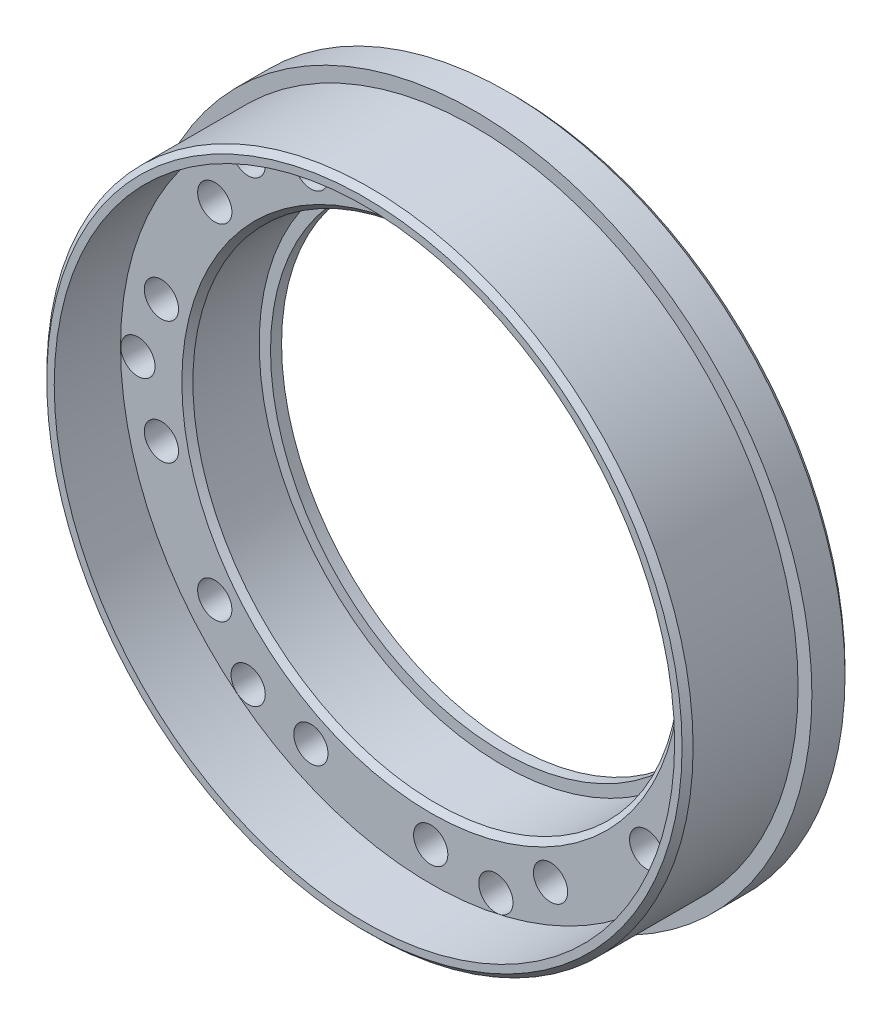
SolidWorks part; units mm, degrees
ref_plane "Front Plane" through (0, 0, 0) normal (0, 0, 1) x (1, 0, 0)
ref_plane "Top Plane" through (0, 0, 0) normal (0, 1, 0) x (1, 0, 0)
ref_plane "Right Plane" through (0, 0, 0) normal (1, 0, 0) x (0, 0, -1)
sketch "Sketch1" plane through (0, 0, 0) normal (0, 0, 1) x (1, 0, 0)
  line L0 (0, 0) -> (0, 34.3477) construction
  circle A0 centre (0, 0) radius 29.25
  circle A1 centre (0, 0) radius 30.5
  circle A2 centre (0, 0) radius 22.025
  circle A3 centre (0, 25) radius 1.55
  circle A4 centre (10.8471, 22.5242) radius 1.55
  circle A5 centre (19.5458, 15.5872) radius 1.55
  circle A6 centre (24.3732, 5.563) radius 1.55
  circle A7 centre (24.3732, -5.563) radius 1.55
  circle A8 centre (19.5458, -15.5872) radius 1.55
  circle A9 centre (10.8471, -22.5242) radius 1.55
  circle A10 centre (0, -25) radius 1.55
  circle A11 centre (-10.8471, -22.5242) radius 1.55
  circle A12 centre (-19.5458, -15.5872) radius 1.55
  circle A13 centre (-24.3732, -5.563) radius 1.55
  circle A14 centre (-24.3732, 5.563) radius 1.55
  circle A15 centre (-19.5458, 15.5872) radius 1.55
  circle A16 centre (-10.8471, 22.5242) radius 1.55
  point P29 (0, 0)
  dimension "D1" = 58.5
  dimension "D2" = 61
  dimension "D3" = 44.05
  dimension "D5" = 3.1
  dimension "D6" = 14
  dimension "D4" = 25
extrude "Boss-Extrude1" add sketch "Sketch1" along normal blind 3.5 contours A0 A1 | A2 A3 A0 A16 A15 A14 A13 A12 A11 A10 A9 A8 A7 A6 A5 A4 | A13 | A14 | A15 | A16 | L0 A3 | A3 L0 | A4 | A5 | A6 | A7 | A8 | A9 | A10 | A11 | A12 region at (20.0979, 20.0979, 0) region at (20.9568, 20.9568, 0) region at (-0.6578, 25, 0) region at (0.6578, 25, 0) region at (10.8471, 22.5242, 0) region at (19.5458, 15.5872, 0) region at (24.3732, 5.563, 0) region at (24.3732, -5.563, 0) region at (19.5458, -15.5872, 0) region at (10.8471, -22.5242, 0) region at (0, -25, 0) region at (-10.8471, -22.5242, 0) region at (-19.5458, -15.5872, 0) region at (-24.3732, -5.563, 0) region at (-24.3732, 5.563, 0) region at (-19.5458, 15.5872, 0) region at (-10.8471, 22.5242, 0)
extrude "lapvsrotor" add sketch "Sketch1<8>" along normal blind 10 from surface contours A2 A3 A0 A16 A15 A14 A13 A12 A11 A10 A9 A8 A7 A6 A5 A4 | A13 | A12 | A11 | A10 | A9 | A7 | A6 | A5 | A4 | A3 L0 | L0 A3 | A16 | A15 | A14 | A8 region at (20.0979, 20.0979, 0) region at (-0.6578, 25, 0) region at (0.6578, 25, 0) region at (10.8471, 22.5242, 0) region at (19.5458, 15.5872, 0) region at (24.3732, 5.563, 0) region at (24.3732, -5.563, 0) region at (19.5458, -15.5872, 0) region at (10.8471, -22.5242, 0) region at (0, -25, 0) region at (-10.8471, -22.5242, 0) region at (-19.5458, -15.5872, 0) region at (-24.3732, -5.563, 0) region at (-24.3732, 5.563, 0) region at (-19.5458, 15.5872, 0) region at (-10.8471, 22.5242, 0) starting at face at (30.5, 0, 3.5)
sketch "Sketch1<8>" plane through (0, 0, 0) normal (0, 0, 1) x (1, 0, 0) same geometry as "Sketch1"
extrude "Cut-Extrude1" cut sketch "Sketch1<9>" against normal blind 10 from surface contours A13 | A12 | A11 | A10 | A9 | A8 | A14 | A15 | A16 | A4 | A5 | A6 | A7 | A3 region at (10.8471, 22.5242, 0) region at (19.5458, 15.5872, 0) region at (24.3732, 5.563, 0) region at (24.3732, -5.563, 0) region at (19.5458, -15.5872, 0) region at (10.8471, -22.5242, 0) region at (0, -25, 0) region at (-10.8471, -22.5242, 0) region at (-19.5458, -15.5872, 0) region at (-24.3732, -5.563, 0) region at (-24.3732, 5.563, 0) region at (-19.5458, 15.5872, 0) region at (-10.8471, 22.5242, 0) starting at face at (29.25, 0, 13.5)
sketch "Sketch1<9>" plane through (0, 0, 0) normal (0, 0, 1) x (1, 0, 0) same geometry as "Sketch1"
sketch "Sketch2" plane through (0, 0, 0) normal (0, 0, 1) x (1, 0, 0)
  circle A0 centre (0, 0) radius 22.05
  circle A1 centre (0, 0) radius 21
  dimension "D1" = 44.1
  dimension "D2" = 42
extrude "Boss-Extrude3" add sketch "Sketch2" along normal blind 1 from surface starting at face at (30.5, 0, 0)
sketch "Sketch3" plane through (0, 0, 0) normal (0, 0, 1) x (1, 0, 0)
  line L0 (0, 0) -> (0, 37.16) construction
  line L1 (0, 0) -> (8.6842, 38.0481) construction
  line L2 (0, 0) -> (39.9985, 19.2623) construction
  line L3 (0, 0) -> (41.5228, 0) construction
  circle A1 centre (0, 0) radius 26.5 construction
  circle A2 centre (5.8968, 25.8356) radius 1.55
  circle A15 centre (23.8757, 11.4979) radius 1.55
  circle A16 centre (23.8757, -11.4979) radius 1.55
  circle A17 centre (5.8968, -25.8356) radius 1.55
  circle A18 centre (-16.5225, -20.7185) radius 1.55
  circle A19 centre (-26.5, 0) radius 1.55
  circle A20 centre (-16.5225, 20.7185) radius 1.55
  point P27 (0, 0)
  point P28 (0, 0)
  dimension "D2" = 53
  dimension "D3" = 3.1
  dimension "D4" = 64.286
  dimension "D1" = 12.857
  dimension "D5" = 7
extrude "Cut-Extrude2" cut sketch "Sketch3" along normal through all from surface starting at face at (30.5, 0, 0)
sketch "Sketch4" plane through (0, 0, 0) normal (0, 0, 1) x (1, 0, 0)
  circle A0 centre (0, 0) radius 28.075
  circle A1 centre (0, 0) radius 21
  dimension "D1" = 56.15
  dimension "D2" = 42
extrude "Cut-Extrude3" cut sketch "Sketch4" against normal blind 6 from surface starting at face at (7.4468, 25.8356, 13.5)
sketch "Sketch5" plane through (0, 0, 0) normal (0, 0, 1) x (1, 0, 0)
  circle A0 centre (5.8968, 25.8356) radius 3
  dimension "D1" = 6
extrude "Cut-Extrude4" cut sketch "Sketch5" along normal blind 2.5 from surface starting at face at (7.4468, 25.8356, 0)
chamfer "Chamfer1" distance 0.5 angle 45 3 edges at (22.025, 0, 7.5) (30.5, 0, 0) (29.25, 0, 13.5)
pattern_circular "CirPattern1" count 7 over 360 about axis through (0, 0, 3.5) along (0, 0, -1) of "Cut-Extrude4"
